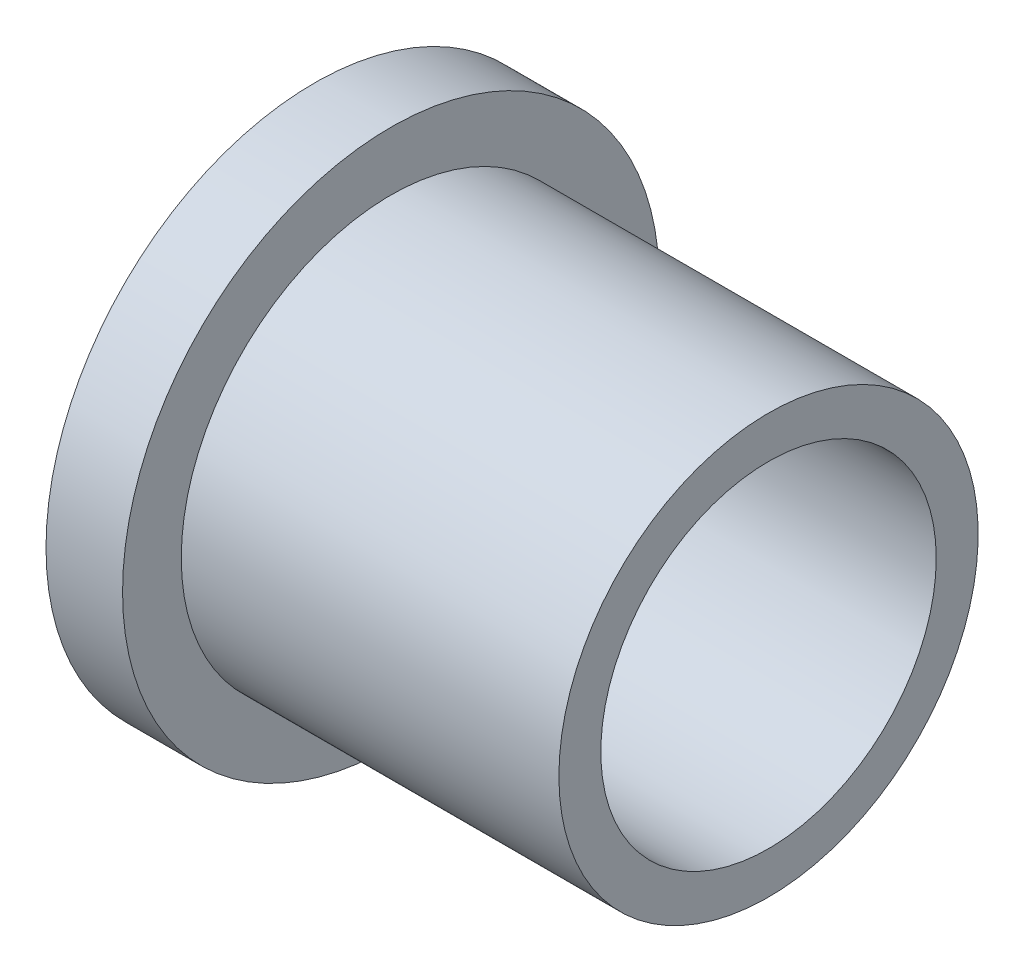
SolidWorks part; units mm, degrees
material "Aluminum Bronze"
ref_plane "Front Plane" through (0, 0, 0) normal (0, 0, 1) x (1, 0, 0)
ref_plane "Top Plane" through (0, 0, 0) normal (0, 1, 0) x (1, 0, 0)
ref_plane "Right Plane" through (0, 0, 0) normal (1, 0, 0) x (0, 0, -1)
sketch "Sketch1" plane through (0, 0, 0) normal (0, 0, 1) x (1, 0, 0)
  line L0 (-46.6574, 0) -> (33.5772, 0) construction
  line L10 (-10.0605, 12.5) -> (12.4547, 12.5)
  line L12 (-10.0605, 0) -> (12.4547, 0)
  line L13 (12.4547, 12.5) -> (12.4547, 0)
  line L14 (-14.6255, 16) -> (-10.0605, 16)
  line L15 (-14.6255, 16) -> (-14.6255, 0)
  line L16 (-14.6255, 0) -> (-10.0605, 0)
  line L17 (-10.0605, 16) -> (-10.0605, 12.5)
  dimension "D1" = 16
  dimension "D2" = 12.5
revolve "Revolve1" add sketch "Sketch1" angle 360 about L0
sketch "Sketch2" plane through (12.4547, 0, 0) normal (1, 0, 0) x (0, 0, -1)
  circle A0 centre (0, 0) radius 10
  dimension "D1" = 20
extrude "Cut-Extrude1" cut sketch "Sketch2" against normal through all
